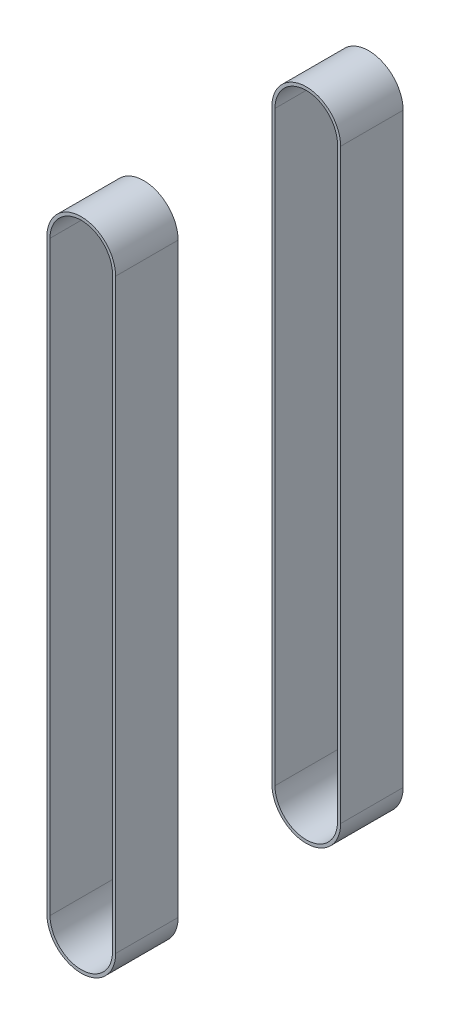
SolidWorks part; units mm, degrees
material "BUTYL"
ref_plane "Plan de face" through (0, 0, 0) normal (0, 0, 1) x (1, 0, 0)
ref_plane "Plan de dessus" through (0, 0, 0) normal (0, 1, 0) x (1, 0, 0)
ref_plane "Plan de droite" through (0, 0, 0) normal (1, 0, 0) x (0, 0, -1)
sketch "Sketch1" plane through (0, 0, 0) normal (0, 0, 1) x (1, 0, 0)
  line L0 (285.2387, 88.4329) -> (285.2416, -30.7688)
  line L1 (297.9387, 88.4332) -> (297.9416, -30.7685)
  line L2 (284.6037, 88.4329) -> (284.6066, -30.7688)
  line L3 (298.5737, 88.4332) -> (298.5766, -30.7685)
  circle A0 centre (291.5916, -30.7687) radius 6.35 construction
  circle A1 centre (291.5887, 88.433) radius 6.35 construction
  arc A2 (285.2416, -30.7688) -> (297.9416, -30.7685) centre (291.5916, -30.7687) ccw
  arc A3 (297.9387, 88.4332) -> (285.2387, 88.4329) centre (291.5887, 88.433) ccw
  arc A4 (284.6066, -30.7688) -> (298.5766, -30.7685) centre (291.5916, -30.7687) ccw
  arc A5 (298.5737, 88.4332) -> (284.6037, 88.4329) centre (291.5887, 88.433) ccw
  dimension "D1" = 0.635
extrude "Boss-Extrude1" add sketch "Sketch1" along normal blind 12.7 from offset 16.51
mirror "Mirror2" about plane through (0, 0, 0) normal (0, 0, 1) of bodies 101
equation "\"Cout/Uni\"= ( ( \"Coût Achat\" + \"Coût Modif\" ) / \"Nb/Paquet\" )"
